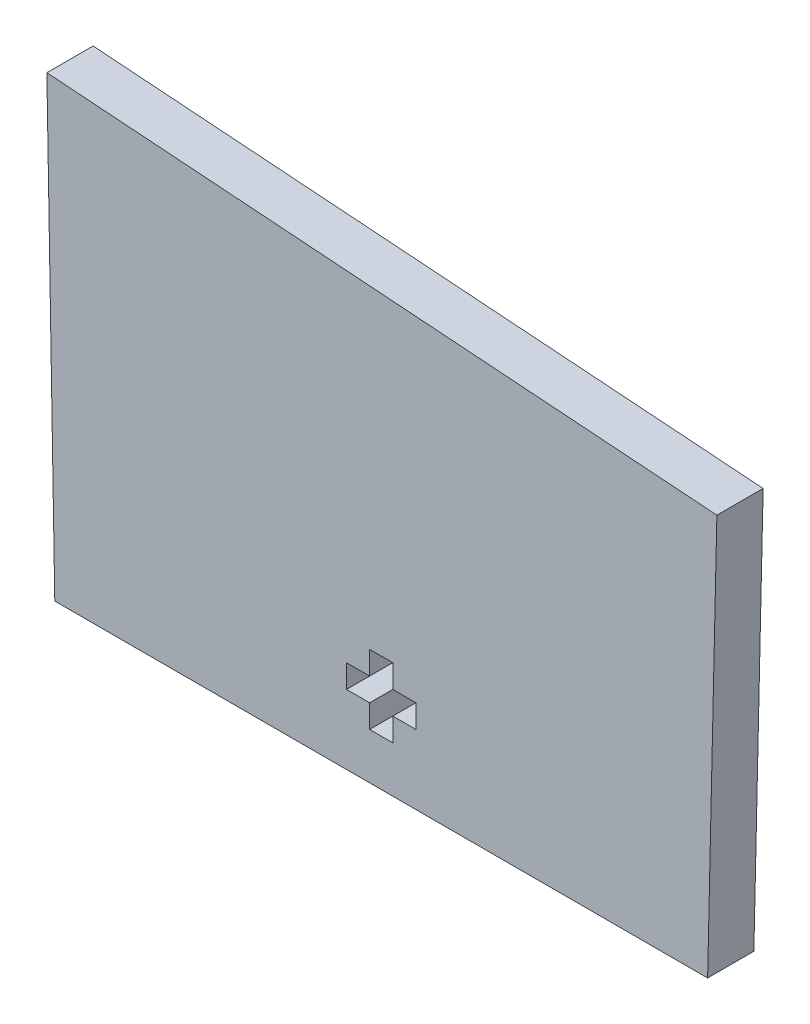
SolidWorks part; units mm, degrees
ref_plane "Ebene vorne" through (0, 0, 0) normal (0, 0, 1) x (1, 0, 0)
ref_plane "Ebene oben" through (0, 0, 0) normal (0, 1, 0) x (1, 0, 0)
ref_plane "Ebene rechts" through (0, 0, 0) normal (1, 0, 0) x (0, 0, -1)
sketch "Skizze1" plane through (0, 0, 0) normal (0, 0, 1) x (1, 0, 0)
  line L0 (0, 0) -> (-0.3424, 19.617)
  line L1 (-0.3424, 19.617) -> (28.631, 17.5334)
  line L2 (28.631, 17.5334) -> (28.23, 0)
  line L3 (28.23, 0) -> (0, 0)
  dimension "D1" = 28.23
  dimension "D2" = 17.538
  dimension "D3" = 19.62
  dimension "D4" = 91
  dimension "D5" = 91.31
extrude "Aufsatz-Linear austragen1" add sketch "Skizze1" along normal blind 2
sketch "Skizze4" plane through (0, 0, 0) normal (0, 0, 1) x (1, 0, 0)
  line L1 (0, 0) -> (30, 0)
  line L2 (0, 0) -> (0, 20)
  line L3 (0, 20) -> (30, 20)
  line L4 (30, 0) -> (30, 20)
  dimension "D1" = 30
  dimension "D2" = 20
sketch "Skizze2" plane through (0, 0, 2) normal (0, 0, 1) x (1, 0, 0)
  circle A0 centre (13.531, 10.0477) radius 16.8536
sketch "Skizze3" plane through (0, 0, 2) normal (0, 0, 1) x (1, 0, 0)
  line L0 (0.1443, -0.2333) -> (28.1443, -0.2333)
  line L1 (0.1443, -0.2333) -> (0.1443, 17.7667)
  line L2 (28.1443, -0.2333) -> (28.1443, 17.7667)
  line L3 (0.1443, 17.7667) -> (28.1443, 17.7667)
  line L4 (0.1443, -0.2333) -> (28.1443, 17.7667) construction
  line L5 (28.1443, -0.2333) -> (0.1443, 17.7667) construction
  line L6 (28.23, 0) -> (28.631, 17.5334) construction
  line L7 (28.631, 17.5334) -> (-0.3424, 19.617) construction
  point P1 (14.1443, 8.7667)
  point P8 (28.4305, 8.7667)
  point P11 (14.1443, 18.5752)
  dimension "D1" = 18
  dimension "D2" = 28
ref_point "SWASI_Vision_Point_1"
ref_point "SWASI_Vision_Point_1_helper"
ref_point "SWASI_Vision_Point_2"
ref_point "SWASI_Vision_Point_2_helper"
ref_point "SWASI_Vision_Point_3"
ref_point "SWASI_Vision_Point_3_helper"
ref_point "SWASI_Vision_Point_4"
ref_plane "SWASI_Alignment_Plane_1" through (0, 0, 0) normal (0, -1, 0) x (-1, 0, 0)
ref_plane "SWASI_Alignment_Plane_2ddasd" through (0, 0, 0) normal (0, 0, 1) x (1, 0, 0)
ref_axis "Achse1" through (28.23, 0, 2) along (-1, 0, 0)
ref_axis "Achse2" through (0, 0, 2) along (0.9975, 0, -0.0707)
ref_axis "Achse3" through (0, 0, 0) along (0.9975, 0, 0.0707)
ref_point "SWASI_Surface_Center_Point"
ref_axis "Achse5" through (0, 0, 2) along (0, 0, -1)
ref_axis "SWASI_Norm_Alignment_Plane_3" through (28.23, 0, 0) along (-1, 0, 0)
ref_plane "SWASI_Alignment_Plane_3" through (14.115, 0, 1) normal (-1, 0, 0) x (0, 0, 1)
ref_point "Punkt1"
ref_point "Punkt2"
sketch "Skizze5" plane through (0, 0, 2) normal (0, 0, 1) x (1, 0, 0)
  line L0 (13.615, 3) -> (12.615, 3)
  line L1 (12.615, 3) -> (12.615, 4)
  line L2 (12.615, 4) -> (13.615, 4)
  line L3 (13.615, 4) -> (13.615, 5)
  line L4 (13.615, 5) -> (14.615, 5)
  line L5 (14.615, 5) -> (14.615, 4)
  line L6 (14.615, 4) -> (15.615, 4)
  line L7 (15.615, 4) -> (15.615, 3)
  line L8 (15.615, 3) -> (14.615, 3)
  line L9 (14.615, 3) -> (14.615, 2)
  line L10 (14.615, 2) -> (13.615, 2)
  line L11 (13.615, 2) -> (13.615, 3)
  line L12 (14.115, 0) -> (14.115, 2)
  line L13 (28.23, 0) -> (0, 0) construction
  point P17 (15.424, 4.4268)
  dimension "D1" = 1
  dimension "D2" = 2
  dimension "D3" = 1
extrude "Schnitt-Linear austragen1" cut sketch "Skizze5" against normal through all contours L11 L10 L9 L8 L7 L6 L5 L4 L3 L2 L1 L0 region at (14.115, 3.5, 2)
